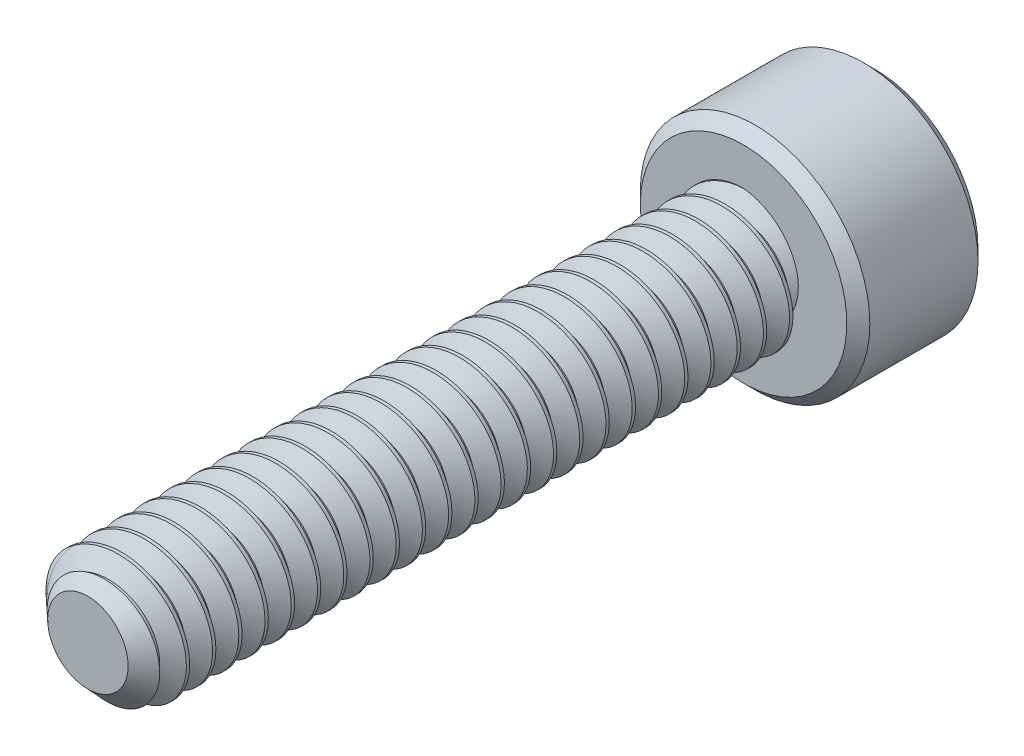
SolidWorks part; units mm, degrees
material "AISI 304"
ref_plane "Front Plane" through (0, 0, 0) normal (0, 0, 1) x (1, 0, 0)
ref_plane "Top Plane" through (0, 0, 0) normal (0, 1, 0) x (1, 0, 0)
ref_plane "Right Plane" through (0, 0, 0) normal (1, 0, 0) x (0, 0, -1)
sketch "Sketch1" plane through (0, 0, 0) normal (0, 0, 1) x (1, 0, 0)
  circle A0 centre (0, 0) radius 2
  dimension "OD" = 4
extrude "Extrude1" add sketch "Sketch1" against normal blind 20
sketch "Sketch2" plane through (0, 0, 0) normal (0, 0, 1) x (1, 0, 0)
  circle A0 centre (0, 0) radius 2 construction
  circle A1 centre (0, 0) radius 2
curve "Helix/Spiral1" pitch 0.8 height 20.8 turns 26 parameters "pitch"=0.8
sketch "Sketch3" plane through (0, 0, 0) normal (1, 0, 0) x (0, 0, -1)
  line L0 (-0.7, 2) -> (-0.4, 1.4804)
  line L1 (-0.4, 1.4804) -> (-0.3, 1.4804)
  line L2 (-0.3, 1.4804) -> (0, 2)
  line L3 (-0.7, 2) -> (0, 2)
  line L4 (-0.35, 2) -> (-0.35, 1.4804) construction
  line L5 (-0.55, 1.7402) -> (-0.15, 1.7402) construction
  line L6 (0, 2) -> (0, -2) construction
  dimension "D1" = 0.1
  dimension "D2" = 0.4
  dimension "D3" = 60
sweep "Cut-Sweep1" cut profiles "Sketch3" path "Helix/Spiral1"
sketch "Sketch4" plane through (0, 0, 0) normal (1, 0, 0) x (0, 0, -1)
  line L0 (0.7214, 2) -> (0, 1.2264)
  line L1 (0, 1.2264) -> (0, 2)
  line L2 (0.7214, 2) -> (0, 2)
  line L3 (-0.7, 2) -> (0, 2) construction
  line L4 (0, 0) -> (7.0209, 0) construction
  dimension "D1" = 47
  dimension "D2" = 0.254
revolve "Cut-Revolve1" cut sketch "Sketch4" angle 360 about L4
sketch "Sketch5" plane through (0, 0, 0) normal (1, 0, 0) x (0, 0, -1)
  line L0 (20, -1.4947) -> (20, 1.4271) construction
  line L1 (20, 2.127) -> (28.1202, 2.127)
  line L2 (20, 2.127) -> (20, 0)
  line L3 (20, 0) -> (28, 0)
  line L4 (28, 1.7968) -> (28, 0)
  line L5 (28.1202, 2.127) -> (28, 1.7968)
  line L6 (0, 0) -> (9.9695, 0) construction
  point P3 (28, 2.127)
  point P10 (28, 2.127)
  dimension "D1" = 0.3302
  dimension "Thread min" = 28
  dimension "D2" = 0.127
  dimension "D3" = 20
revolve "partially thread" [suppressed] add sketch "Sketch5" angle 360 about L6
sketch "Sketch6" plane through (0, 0, -20) normal (0, 0, -1) x (-1, 0, 0)
  circle A0 centre (0, 0) radius 3.5
  dimension "head dia" = 7
extrude "Extrude2" add sketch "Sketch6" along normal blind 4
sketch "Sketch7" plane through (0, 0, -24) normal (0, 0, -1) x (-1, 0, 0)
  line L1 (0, 1.7321) -> (-1.5, 0.866)
  line L2 (-1.5, 0.866) -> (-1.5, -0.866)
  line L3 (-1.5, -0.866) -> (0, -1.7321)
  line L4 (0, -1.7321) -> (1.5, -0.866)
  line L5 (1.5, -0.866) -> (1.5, 0.866)
  line L6 (1.5, 0.866) -> (0, 1.7321)
  circle A0 centre (0, 0) radius 1.5 construction
  dimension "hex dia" = 3
extrude "Cut-Extrude1" cut sketch "Sketch7" against normal blind 2.25
sketch "Sketch8" plane through (0, 0, -24) normal (0, 0, -1) x (-1, 0, 0)
  circle A0 centre (0, 0) radius 1.7321
extrude "Cut-Extrude2" cut sketch "Sketch8" against normal through all draft 45
chamfer "Chamfer1" distance 0.35 angle 45 2 edges at (-3.5, 0, -24) (-3.5, 0, -20)
sketch "Sketch9" plane through (0, 0, 0) normal (1, 0, 0) x (0, 0, -1)
  line L0 (0, 2) -> (0, -2) construction
  line L1 (4.4, 2) -> (4.4, -2) construction
  dimension "D1" = 4.4
  dimension "D4" = 0.635
  dimension "D5" = 0.3302
equation "\"D3@Helix/Spiral1\" = \"screw length@Extrude1\"+\"pitch@Helix/Spiral1\""
equation "\"D1@Sketch3\" = \"pitch@Helix/Spiral1\"*.125"
equation "\"D2@Sketch3\" = \"pitch@Helix/Spiral1\"*.5"
equation "\"D1@Cut-Extrude1\" = \"hex dia@Sketch7\"*.75"
equation "\"D1@Chamfer1\" = \"head dia@Sketch6\"*.05"
equation "\"D1@Sketch9\" = \"pitch@Helix/Spiral1\"*5.5"
